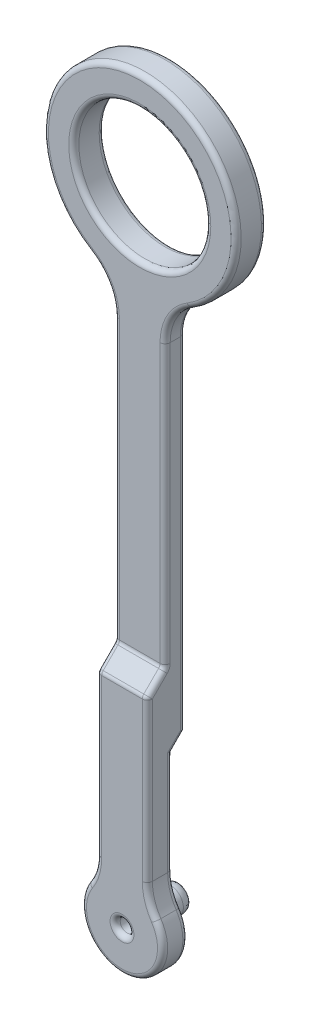
SolidWorks part; units mm, degrees
ref_plane "Front Plane" through (0, 0, 0) normal (0, 0, 1) x (1, 0, 0)
ref_plane "Top Plane" through (0, 0, 0) normal (0, 1, 0) x (1, 0, 0)
ref_plane "Right Plane" through (0, 0, 0) normal (1, 0, 0) x (0, 0, -1)
ref_plane "Plane1" through (0, 0, 10.5) normal (0, 0, 1) x (1, 0, 0)
sketch "Sketch1" plane through (0, 0, 10.5) normal (0, 0, 1) x (1, 0, 0)
  line L0 (5, 66.245) -> (-5, 66.245)
  arc A0 (-5, 66.245) -> (5, 66.245) centre (0, 60) ccw
extrude "Boss-Extrude1" add sketch "Sketch1" against normal blind 3.5
sketch "Sketch2" plane through (0, 66.245, 0) normal (0, 1, 0) x (-1, 0, 0)
  line L0 (-5, 7) -> (-5, 10.5)
  line L1 (-5, 10.5) -> (5, 10.5)
  line L2 (5, 10.5) -> (5, 7)
  line L3 (5, 7) -> (-5, 7)
extrude "Boss-Extrude2" add sketch "Sketch2" along normal blind 100.4247
sketch "Sketch3" plane through (0, 0, 7) normal (0, 0, -1) x (-1, 0, 0)
  line L0 (-5, 66.245) -> (-5, 166.6697)
  line L1 (5, 166.6697) -> (5, 66.245)
  arc A0 (5, 66.245) -> (-5, 66.245) centre (0, 60) cw
  arc A1 (-5, 166.6697) -> (5, 166.6697) centre (0, 185) cw
extrude "Boss-Extrude3" add sketch "Sketch3" along normal blind 1.5
sketch "Sketch4" plane through (0, 166.6697, 0) normal (0, 1, 0) x (-1, 0, 0)
  line L0 (-5, 10.5) -> (-5, 7)
  line L1 (-5, 7) -> (5, 7)
  line L2 (5, 7) -> (5, 10.5)
  line L3 (5, 10.5) -> (-5, 10.5)
extrude "Cut-Extrude1" cut sketch "Sketch4" against normal blind 61.6697
sketch "Sketch5" plane through (0, 0, 5.5) normal (0, 0, -1) x (-1, 0, 0)
  line L0 (5, 166.6697) -> (5, 92.5)
  line L1 (5, 92.5) -> (-5, 92.5)
  line L2 (-5, 92.5) -> (-5, 166.6697)
  arc A0 (-5, 166.6697) -> (5, 166.6697) centre (0, 185) cw
extrude "Boss-Extrude4" add sketch "Sketch5" along normal blind 2.5
sketch "Sketch6" plane through (0, 0, 3) normal (0, 0, -1) x (-1, 0, 0)
  circle A0 centre (0, 185) radius 19
extrude "Boss-Extrude5" add sketch "Sketch6" along normal blind 2
draft "Draft1" type of draft neutral plane draft angle 45 faces to draft 1 face at (0, 92.5, 4.25) neutral plane through (0, 185, 3) neutral plane normal (0, 0, -1) parameters "D1"=45
draft "Draft2" type of draft neutral plane draft angle 45 faces to draft 1 face at (0, 105, 8.75) neutral plane through (0, 60, 7) neutral plane normal (0, 0, 1) parameters "D1"=45
ref_plane "Plane2" through (0, 60, 0) normal (0, -1, 0) x (1, 0, 0)
sketch "Sketch7" plane through (0, 60, 0) normal (0, -1, 0) x (1, 0, 0)
  line L0 (2, 5.5) -> (0, 5.5)
  line L1 (0, 5.5) -> (0, 5)
  line L2 (0, 5) -> (2, 5)
  line L3 (2, 5) -> (2, 5.5)
  line L4 (0, 5.5) -> (0, 5) construction
revolve "Revolve1" add sketch "Sketch7" angle 360 about L4 reverse direction yes
hole_wizard "HoleWzd1" positions "Sketch9" profile "Sketch8" counterbore size "M25" standard "ANSI Metric"
sketch "Sketch9" plane through (0, 0, 7) normal (0, 0, 1) x (1, 0, 0)
  point P0 (0, 185)
sketch "Sketch8" plane through (0, 185, 7) normal (1, 0, 0) x (0, -1, 0)
  line L0 (0, 0) -> (0, 6)
  line L1 (0, 6) -> (14.5, 6)
  line L3 (14.5, 6) -> (14.5, 5.5)
  line L4 (14.5, 5.5) -> (16, 5.5)
  line L5 (16, 5.5) -> (16, 0)
  line L7 (16, 0) -> (0, 0)
  line L11 (0, -6.35) -> (0, 107.95) construction
  dimension "Thru Hole Dia." = 29
  dimension "Thru Hole Depth" = 6
  dimension "C'Bore Dia." = 32
  dimension "C'Bore Depth" = 5.5
hole_wizard "HoleWzd2" positions "Sketch11" profile "Sketch10" hole size "Ø3.0" standard "ANSI Metric"
sketch "Sketch11" plane through (0, 0, 5) normal (0, 0, -1) x (-1, 0, 0)
  point P0 (0, 60)
sketch "Sketch10" plane through (0, 60, 5) normal (1, 0, 0) x (0, 1, 0)
  line L0 (0, 0) -> (0, 5.5)
  line L1 (0, 5.5) -> (1.5, 5.5)
  line L2 (1.5, 5.5) -> (1.5, 0)
  line L5 (1.5, 0) -> (0, 0)
  line L11 (0, -6.35) -> (0, 107.95) construction
  dimension "Thru Hole Dia." = 3
  dimension "Thru Hole Depth" = 5.5
fillet "Fillet1" radius 10 4 edges at (-5, 166.6697, 5) (5, 166.6697, 5) (5, 66.245, 8) (-5, 66.245, 8) tangent propagation no
sketch "Sketch12" plane through (0, 0, 10.5) normal (0, 0, 1) x (1, 0, 0)
  circle A0 centre (0, 60) radius 2.6
  circle A1 centre (0, 60) radius 1.5 construction
  dimension "D1" = 5.2
extrude "Boss-Extrude6" add sketch "Sketch12" against normal offset from surface (11 mm away) 6 up to face at (-2, 60, 5.5) offset beyond the face yes
sketch "Sketch13" plane through (0, 0, 7) normal (0, 0, 1) x (1, 0, 0)
  circle A0 centre (0, 185) radius 16 construction
  circle A1 centre (0, 185) radius 16
extrude "Boss-Extrude7" add sketch "Sketch13" against normal up to surface (6 mm away) up to face at (14.5, 185, 1)
sketch "Sketch14" plane through (0, 0, 1) normal (0, 0, -1) x (-1, 0, 0)
  circle A0 centre (0, 185) radius 13
  arc A1 (9.8276, 168.739) -> (-9.8276, 168.739) centre (0, 185) ccw construction
  dimension "D1" = 26
extrude "Cut-Extrude2" cut sketch "Sketch14" against normal blind 10
fillet "Fillet2" radius 1 2 edges at (13, 185, 7) (-13, 185, 1)
fillet "Fillet3" radius 1.5 1 edges at (2.6, 60, -0.5) second distance 0.5 first distance on face at (2.6, 60, -0.5)
sketch "Sketch16" plane through (0, 0, -0.5) normal (0, 0, -1) x (-1, 0, 0)
  circle A0 centre (0, 60) radius 1.35
  circle A2 centre (0, 60) radius 2.6 construction
  dimension "D1" = 2.7
extrude "Cut-Extrude4" cut sketch "Sketch16" against normal through all
fillet "Fillet4" radius 1 1 edges at (-1.35, 60, 10.5)
sketch "Sketch17" plane through (0, 0, 5.5) normal (0, 0, -1) x (-1, 0, 0)
  circle A0 centre (0, 60) radius 3.4
  circle A1 centre (0, 60) radius 1.35 construction
  circle A2 centre (0, 60) radius 2.6 construction
  circle A3 centre (0, 60) radius 1.35
  dimension "D1" = 0.8
extrude "Boss-Extrude8" add sketch "Sketch17" along normal blind 1
fillet "Fillet5" radius 1 27 edges at (5, 103.25, 8.75) (-5, 103.25, 8.75) (-6.2901, 165.0937, 3) (6.2901, 165.0937, 3) (5, 79.9749, 5.5) (5.4257, 67.0631, 5.5) (0, 52, 5.5) (-5.4257, 67.0631, 5.5) (5.4257, 67.0631, 10.5) (0, 52, 10.5) (-5.4257, 67.0631, 10.5) (-5, 85.7249, 10.5) (0, 101.5, 10.5) (5, 85.7249, 10.5) (-19, 185, 1) (6.2901, 165.0937, 7) (5, 132.5903, 7) (0, 105, 7) (-5, 132.5903, 7) (-6.2901, 165.0937, 7) (0, 204, 7) (-5, 91.25, 4.25) (-5, 126.3403, 3) (5, 126.3403, 3) (5, 91.25, 4.25) (-5, 79.9749, 5.5) (3.4, 60, 5.5)
